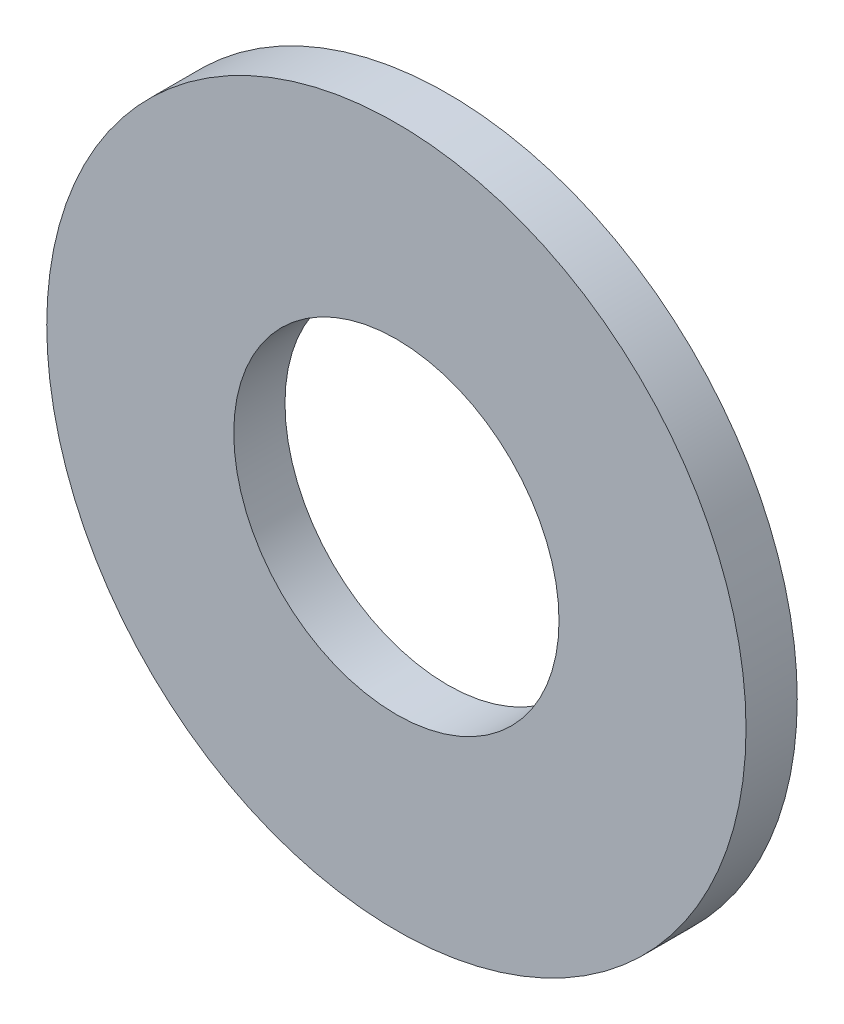
SolidWorks part; units mm, degrees
material "Brass"
ref_plane "Front" through (0, 0, 0) normal (0, 0, 1) x (1, 0, 0)
ref_plane "Top" through (0, 0, 0) normal (0, 1, 0) x (1, 0, 0)
ref_plane "Right" through (0, 0, 0) normal (1, 0, 0) x (0, 0, -1)
ref_axis "side-side" through (80.9, 0, 0) along (-1, 0, 0)
ref_axis "up-down" through (0, 50, 0) along (0, -1, 0)
ref_axis "front-back" through (0, 0, -80.9) along (0, 0, 1)
sketch "Sketch1" plane through (0, 0, 0) normal (1, 0, 0) x (0, 0, -1)
  line L0 (0, 0) -> (45.9347, 0) construction
  line L1 (0, 5.461) -> (0.8001, 5.461)
  line L2 (0, 5.461) -> (0, 2.54)
  line L3 (0, 2.54) -> (0.8001, 2.54)
  line L4 (0.8001, 5.461) -> (0.8001, 2.54)
  line L5 (0, 50) -> (0, -50) construction
  dimension "D1" = 5.08
  dimension "D2" = 10.922
  dimension "D3" = 0.8001
revolve "Revolve1" add sketch "Sketch1" angle 360 about L0
